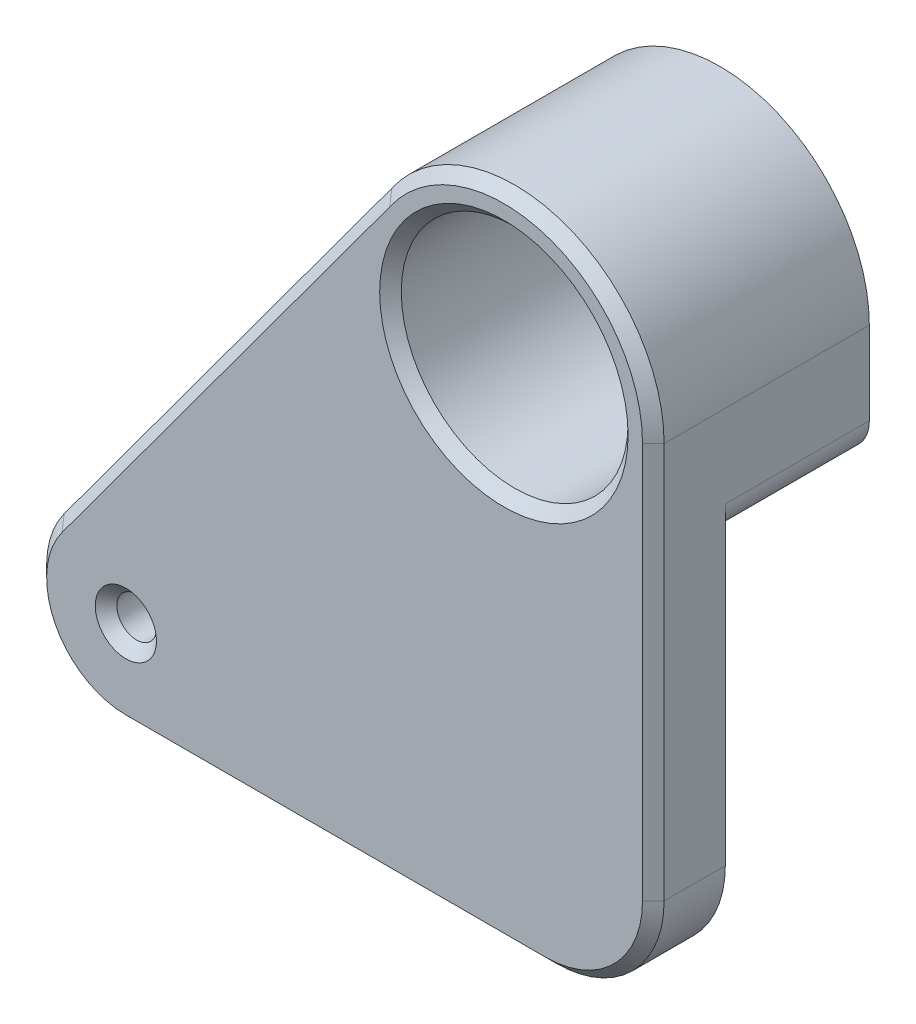
SolidWorks part; units mm, degrees
ref_plane "Front Plane" through (0, 0, 0) normal (0, 0, 1) x (1, 0, 0)
ref_plane "Top Plane" through (0, 0, 0) normal (0, 1, 0) x (1, 0, 0)
ref_plane "Right Plane" through (0, 0, 0) normal (1, 0, 0) x (0, 0, -1)
sketch "Sketch1" plane through (0, 0, 0) normal (0, 0, 1) x (1, 0, 0)
  line L0 (296.5, 0) -> (300, 0)
  line L3 (296.5, 8) -> (300, 8)
  line L4 (296.5, 41) -> (296.5, -69)
  line L5 (150, -99) -> (266.5, -99)
  line L6 (220.8686, 64.6072) -> (129.8574, -59.1921)
  circle A1 centre (150, -74) radius 5.5
  circle A2 centre (255, 41) radius 31.5
  arc A3 (129.8574, -59.1921) -> (150, -99) centre (150, -74) ccw
  arc A4 (296.5, 41) -> (220.8686, 64.6072) centre (255, 41) ccw
  circle A6 centre (255, 41) radius 41.5 construction
  arc A7 (296.5, -69) -> (266.5, -99) centre (266.5, -69) cw
  circle A9 centre (150, -74) radius 25 construction
  point P3 (210, 0)
  point P5 (210, 8)
  point P13 (294.6866, 53.1334)
  point P23 (175, -74)
  dimension "D1" = 30
  dimension "D3" = 10
extrude "Boss-Extrude1" add sketch "Sketch1" along normal blind 20 contours A7 L4 A4 L6 A3 L5 A2 A1
sketch "Sketch2" plane through (0, 0, 0) normal (0, 0, -1) x (-1, 0, 0)
  line L4 (-296.5, 41) -> (-296.5, -69) construction
  line L5 (-300, 8) -> (300, 8)
  line L6 (-296.5, 8) -> (-179.2537, 8)
  line L7 (-220.8686, 64.6072) -> (-129.8574, -59.1921) construction
  line L8 (-296.5, 41) -> (-296.5, 8)
  line L9 (-220.8686, 64.6072) -> (-179.2537, 8)
  circle A3 centre (-255, 41) radius 31.5 construction
  arc A4 (-220.8686, 64.6072) -> (-296.5, 41) centre (-255, 41) ccw construction
  circle A5 centre (-255, 41) radius 31.5
  arc A6 (-220.8686, 64.6072) -> (-296.5, 41) centre (-255, 41) ccw
  dimension "D1" = 8
extrude "Boss-Extrude2" add sketch "Sketch2" along normal blind 40
chamfer "Chamfer1" distance 3 angle 45 8 edges at (155.5, -74, 20) (286.5, 41, 20) (208.25, -99, 20) (127.6931, -85.2872, 20) (175.363, 2.7075, 20) (267.3652, 80.615, 20) (296.5, -14, 20) (287.7132, -90.2132, 20)
fillet "Fillet1" radius 10 2 edges at (296.5, 8, -20) (179.2537, 8, -20)
